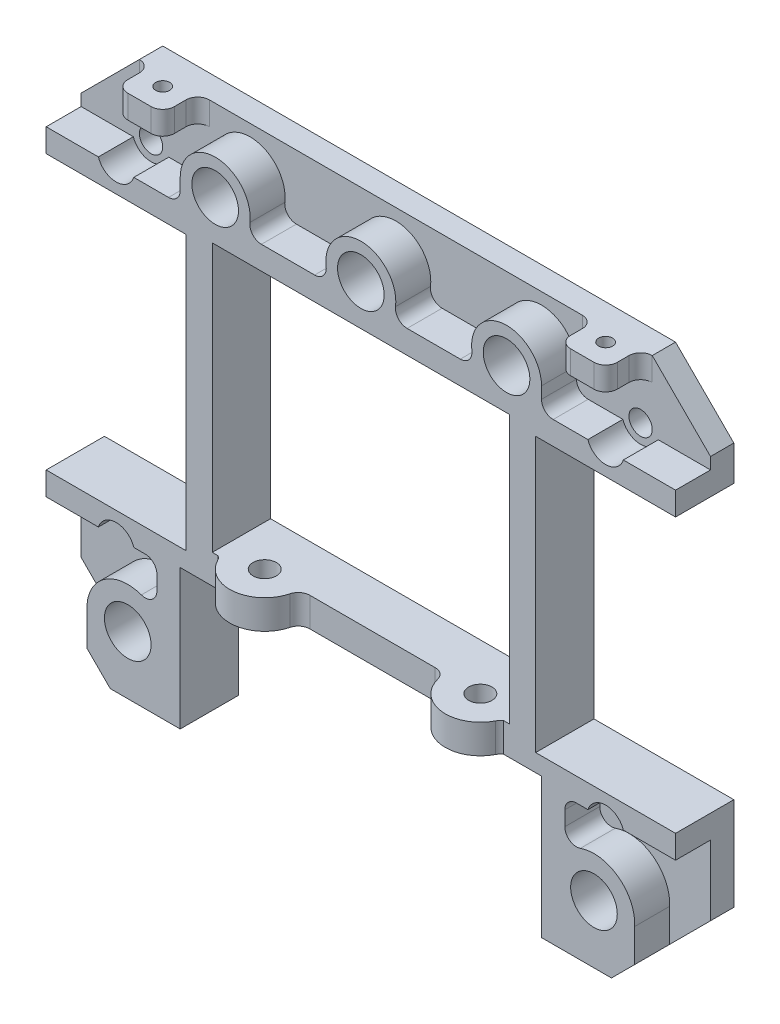
SolidWorks part; units mm, degrees
ref_plane "前视基准面" through (0, 0, 0) normal (0, 0, 1) x (1, 0, 0)
ref_plane "上视基准面" through (0, 0, 0) normal (0, 1, 0) x (1, 0, 0)
ref_plane "右视基准面" through (0, 0, 0) normal (1, 0, 0) x (0, 0, -1)
sketch "草图1" plane through (0, 0, 0) normal (0, 0, 1) x (1, 0, 0)
  line L0 (0, 54.5254) -> (0, -46.9226) construction
  line L1 (77.1188, 0) -> (-86.5987, 0) construction
  line L2 (-27, 25) -> (-15, 25)
  line L3 (-15, 25) -> (-15, 1.5)
  line L4 (-15, 1.5) -> (-27, 1.5)
  line L5 (-27, 1.5) -> (-27, -6.5)
  line L6 (-27, -6.5) -> (-21.5, -12)
  line L7 (-21.5, -12) -> (-15.5, -12)
  line L8 (-15.5, -12) -> (-15.5, 0)
  line L9 (-15.5, 0) -> (15.5, 0)
  line L10 (-27, 25) -> (-27, 28)
  line L11 (-22, 33) -> (22, 33)
  line L12 (-12.75, 25.5) -> (-12.75, 2.5)
  line L13 (-12.75, 2.5) -> (12.75, 2.5)
  line L14 (12.75, 25.5) -> (-12.75, 25.5)
  line L15 (15.5, -12) -> (15.5, 0)
  line L16 (21.5, -12) -> (15.5, -12)
  line L17 (15, 1.5) -> (27, 1.5)
  line L18 (27, 1.5) -> (27, -6.5)
  line L19 (15, 25) -> (15, 1.5)
  line L20 (27, 25) -> (27, 28)
  line L21 (12.75, 25.5) -> (12.75, 2.5)
  line L22 (15, 25) -> (27, 25)
  line L23 (21.5, -12) -> (27, -6.5)
  line L24 (-27, 28) -> (-22, 33)
  line L25 (27, 28) -> (22, 33)
  circle A0 centre (20, -7) radius 2
  circle A1 centre (12.5, 29) radius 2
  circle A2 centre (0, 29) radius 2
  circle A3 centre (-20, -7) radius 2
  circle A4 centre (-12.5, 29) radius 2
  circle A5 centre (21, 27.5) radius 1
  circle A6 centre (21, -1) radius 1
  circle A7 centre (-21, 27.5) radius 1
  circle A8 centre (-21, -1) radius 1
  point P36 (0, 36)
  point P37 (-27, 33)
  point P40 (0, 0)
  point P41 (0, 0)
  point P48 (27, 33)
  point P50 (0, 25.5)
  dimension "D1" = 4
  dimension "D2" = 4
  dimension "D3" = 4
  dimension "D10" = 2
  dimension "D11" = 2
  dimension "D4" = 28.5
  dimension "D5" = 42
  dimension "D6" = 40
  dimension "D7" = 25
  dimension "D8" = 7
  dimension "D9" = 1
  dimension "D12" = 29
  dimension "D13" = 15.5
  dimension "D14" = 2.5
  dimension "D15" = 6
  dimension "D16" = 2.5
  dimension "D17" = 23
  dimension "D18" = 6
  dimension "D19" = 6
  dimension "D20" = 12
  dimension "D21" = 2.5
  dimension "D23" = 45
  dimension "D24" = 25.5
extrude "凸台-拉伸1" add sketch "草图1" along normal blind 2
sketch "草图3" plane through (0, 2.5, 0) normal (0, 1, 0) x (1, 0, 0)
  line L0 (0, 0) -> (0, -8.4944) construction
  line L1 (22, 0) -> (-22, 0) construction
  line L2 (-9.25, 1.7097) -> (-9.25, -4) construction
  line L3 (-6.25, -2) -> (-6.25, -4)
  line L4 (22, -2) -> (-22, -2) construction
  line L5 (-12.25, -2) -> (-12.25, -4)
  line L6 (-12.25, -2) -> (-6.25, -2)
  line L7 (12.25, -2) -> (6.25, -2)
  line L8 (12.25, -2) -> (12.25, -4)
  line L9 (6.25, -2) -> (6.25, -4)
  circle A0 centre (-9.25, -4) radius 1
  arc A1 (-12.25, -4) -> (-6.25, -4) centre (-9.25, -4) ccw
  arc A2 (12.25, -4) -> (6.25, -4) centre (9.25, -4) cw
  circle A3 centre (9.25, -4) radius 1
  dimension "D3" = 2
  dimension "D4" = 3
  dimension "D1" = 4
  dimension "D2" = 18.5
extrude "凸台-拉伸2" add sketch "草图3" against normal blind 2.5
sketch "草图4" plane through (0, 0, 2) normal (0, 0, 1) x (1, 0, 0)
  line L2 (-15.5, 29) -> (-15.5, 27)
  line L5 (-9.9019, 27.5) -> (-2.5981, 27.5)
  line L9 (2.5981, 27.5) -> (9.9019, 27.5)
  line L10 (15.5, 29) -> (15.5, 27)
  line L11 (-19.4801, -0.5) -> (-17.5, -0.5)
  line L12 (-17.5, -0.5) -> (-17.5, -4.5505)
  line L14 (-22.5199, -0.5) -> (-25, -0.5)
  line L15 (-25, -0.5) -> (-25, -5.6716) construction
  line L16 (-25, -5.6716) -> (-23.4956, -7.176) construction
  line L17 (0, 0) -> (0, -5.4356) construction
  line L18 (19.4801, -0.5) -> (17.5, -0.5)
  line L19 (17.5, -0.5) -> (17.5, -4.5505)
  line L21 (25, -5.6716) -> (23.4956, -7.176) construction
  line L22 (25, -0.5) -> (25, -5.6716) construction
  line L23 (22.5199, -0.5) -> (25, -0.5)
  line L24 (25, -0.5) -> (27, -0.5)
  line L25 (-25, -0.5) -> (-27, -0.5)
  line L26 (-23.4956, -7.176) -> (-23.4956, -10.0044)
  line L27 (23.4956, -7.176) -> (23.4956, -10.0044)
  line L28 (-15.5, 27) -> (-19.4801, 27)
  line L30 (-27, 27) -> (-27, 25)
  line L31 (-27, 25) -> (-16.5, 25)
  line L32 (27, 25) -> (16.5, 25)
  line L33 (15.5, 27) -> (19.4801, 27)
  line L34 (27, 27) -> (27, 25)
  line L35 (12.25, 2.5) -> (12.25, 0)
  line L36 (12.25, 0) -> (15.5, 0)
  line L37 (15.5, 0) -> (15.5, -12)
  line L38 (15.5, -12) -> (21.5, -12)
  line L39 (21.5, -12) -> (27, -6.5)
  line L40 (27, -6.5) -> (27, 1.5)
  line L41 (27, 1.5) -> (15, 1.5)
  line L42 (15, 1.5) -> (15, 25)
  line L43 (15, 25) -> (27, 25)
  line L44 (27, 25) -> (27, 28)
  line L45 (27, 28) -> (22, 33)
  line L46 (22, 33) -> (-22, 33)
  line L47 (-22, 33) -> (-27, 28)
  line L48 (-27, 28) -> (-27, 25)
  line L49 (-27, 25) -> (-15, 25)
  line L50 (-15, 25) -> (-15, 1.5)
  line L51 (-15, 1.5) -> (-27, 1.5)
  line L52 (-27, 1.5) -> (-27, -6.5)
  line L53 (-27, -6.5) -> (-21.5, -12)
  line L54 (-21.5, -12) -> (-15.5, -12)
  line L55 (-15.5, -12) -> (-15.5, 0)
  line L84 (-15.5, 0) -> (-12.25, 0)
  line L85 (-12.25, 0) -> (-12.25, 2.5)
  line L86 (-12.25, 2.5) -> (-12.75, 2.5)
  line L87 (-12.75, 2.5) -> (-12.75, 25.5)
  line L88 (-12.75, 25.5) -> (12.75, 25.5)
  line L89 (12.75, 25.5) -> (12.75, 2.5)
  line L90 (12.75, 2.5) -> (12.25, 2.5)
  line L91 (12.25, 2.5) -> (12.25, 0)
  line L92 (12.25, 0) -> (15.5, 0)
  line L93 (15.5, 0) -> (15.5, -12)
  line L94 (15.5, -12) -> (21.5, -12)
  line L95 (21.5, -12) -> (23.4956, -10.0044)
  line L96 (27, -0.5) -> (27, 1.5)
  line L97 (27, 1.5) -> (15, 1.5)
  line L98 (15, 1.5) -> (15, 25)
  line L99 (15, 25) -> (16.5, 25)
  line L105 (-16.5, 25) -> (-15, 25)
  line L106 (-15, 25) -> (-15, 1.5)
  line L107 (-15, 1.5) -> (-27, 1.5)
  line L108 (-27, 1.5) -> (-27, -0.5)
  line L109 (-23.4956, -10.0044) -> (-21.5, -12)
  line L110 (-21.5, -12) -> (-15.5, -12)
  line L111 (-15.5, -12) -> (-15.5, 0)
  line L112 (-15.5, 0) -> (-12.25, 0)
  line L113 (-12.25, 0) -> (-12.25, 2.5)
  line L114 (-12.25, 2.5) -> (-12.75, 2.5)
  line L115 (-12.75, 2.5) -> (-12.75, 25.5)
  line L116 (-12.75, 25.5) -> (12.75, 25.5)
  line L117 (12.75, 25.5) -> (12.75, 2.5)
  line L118 (12.75, 2.5) -> (12.25, 2.5)
  line L119 (-22.5199, 27) -> (-27, 27)
  line L120 (22.5199, 27) -> (27, 27)
  line L121 (-21, 33) -> (-21, 31)
  line L122 (22, 33) -> (-22, 33) construction
  line L123 (-17, 33) -> (-17, 31)
  line L124 (-17, 31) -> (-21, 31)
  line L125 (-17, 33) -> (-21, 33)
  line L126 (17, 33) -> (21, 33)
  line L127 (17, 31) -> (21, 31)
  line L128 (17, 33) -> (17, 31)
  line L129 (21, 33) -> (21, 31)
  arc A2 (-19.4801, -0.5) -> (-22.5199, -0.5) centre (-21, -1) ccw
  arc A3 (22.5199, -0.5) -> (19.4801, -0.5) centre (21, -1) ccw
  circle A5 centre (-20, -7) radius 2 construction
  circle A6 centre (20, -7) radius 2 construction
  circle A7 centre (12.5, 29) radius 2 construction
  circle A8 centre (0, 29) radius 2 construction
  circle A9 centre (-12.5, 29) radius 2 construction
  circle A10 centre (20, -7) radius 2
  circle A11 centre (12.5, 29) radius 2
  circle A12 centre (0, 29) radius 2
  circle A13 centre (-12.5, 29) radius 2
  circle A14 centre (-20, -7) radius 2
  arc A15 (-9.9019, 27.5) -> (-15.5, 29) centre (-12.5, 29) ccw
  arc A16 (2.5981, 27.5) -> (-2.5981, 27.5) centre (0, 29) ccw
  arc A17 (15.5, 29) -> (9.9019, 27.5) centre (12.5, 29) ccw
  arc A18 (-23.4956, -7.176) -> (-17.5, -4.5505) centre (-20, -7) cw
  arc A19 (23.4956, -7.176) -> (17.5, -4.5505) centre (20, -7) ccw
  arc A20 (-22.5199, 27) -> (-19.4801, 27) centre (-21, 27.5) ccw
  arc A21 (22.5199, 27) -> (19.4801, 27) centre (21, 27.5) cw
  dimension "D2" = 2
  dimension "D3" = 2
  dimension "D4" = 3.2
  dimension "D5" = 3.2
  dimension "D6" = 4
  dimension "D7" = 6
  dimension "D8" = 6
  dimension "D12" = 1.5
  dimension "D14" = 3.2
  dimension "D9" = 2
  dimension "D10" = 2
  dimension "D11" = 2
  dimension "D13" = 2
  dimension "D15" = 2
  dimension "D1" = 0
extrude "凸台-拉伸3" add sketch "草图4" along normal blind 3
fillet "圆角1" radius 1 18 edges at (17.5, -0.5, 3.5) (17.5, -4.5505, 3.5) (-17.5, -4.5505, 3.5) (-17.5, -0.5, 3.5) (9.9019, 27.5, 3.5) (2.5981, 27.5, 3.5) (-2.5981, 27.5, 3.5) (-9.9019, 27.5, 3.5) (15.5, 27, 3.5) (-15.5, 27, 3.5) (-21, 32, 5) (-17, 32, 5) (17, 32, 5) (21, 32, 5) (21, 32, 2) (17, 32, 2) (-17, 32, 2) (-21, 32, 2)
fillet "圆角2" radius 1 2 edges at (-12.25, 1.25, 4) (12.25, 1.25, 4)
sketch "草图5" plane through (0, 0, 2) normal (0, 0, 1) x (1, 0, 0)
  line L4 (6.25, 0) -> (6.25, 2.5)
  line L5 (6.25, 2.5) -> (-6.25, 2.5)
  line L6 (-6.25, 2.5) -> (-6.25, 0)
  line L7 (-6.25, 0) -> (6.25, 0)
  line L8 (6.25, 0) -> (6.25, 2.5)
  line L9 (6.25, 2.5) -> (-6.25, 2.5)
  line L10 (-6.25, 2.5) -> (-6.25, 0)
  line L11 (-6.25, 0) -> (6.25, 0)
  dimension "D1" = 0
extrude "凸台-拉伸4" add sketch "草图5" along normal blind 2
fillet "圆角3" radius 1 2 edges at (6.25, 1.25, 4) (-6.25, 1.25, 4)
sketch "草图6" plane through (0, 0, 0) normal (0, -1, 0) x (1, 0, 0)
  circle A0 centre (-9.25, 4) radius 2
  circle A1 centre (9.25, 4) radius 2
  dimension "D1" = 4
  dimension "D2" = 4
extrude "切除-拉伸1" cut sketch "草图6" against normal blind 1
sketch "草图7" plane through (0, -12, 0) normal (0, -1, 0) x (1, 0, 0)
  line L0 (0, 0) -> (0, 11.3884) construction
  line L1 (-15.5, 0) -> (15.5, 0) construction
  circle A0 centre (19, 2.5) radius 0.75
  circle A1 centre (-19, 2.5) radius 0.75
  dimension "D1" = 1.5
  dimension "D2" = 19
  dimension "D3" = 2.5
extrude "切除-拉伸2" cut sketch "草图7" against normal blind 2.5
sketch "草图8" plane through (0, 33, 0) normal (0, 1, 0) x (1, 0, 0)
  line L0 (0, 0) -> (0, -8.4556) construction
  line L1 (20, -5) -> (18, -5) construction
  circle A0 centre (-19, -3) radius 0.6
  circle A1 centre (19, -3) radius 0.6
  dimension "D3" = 1.2
  dimension "D1" = 19
  dimension "D2" = 2
extrude "切除-拉伸3" cut sketch "草图8" against normal blind 3
